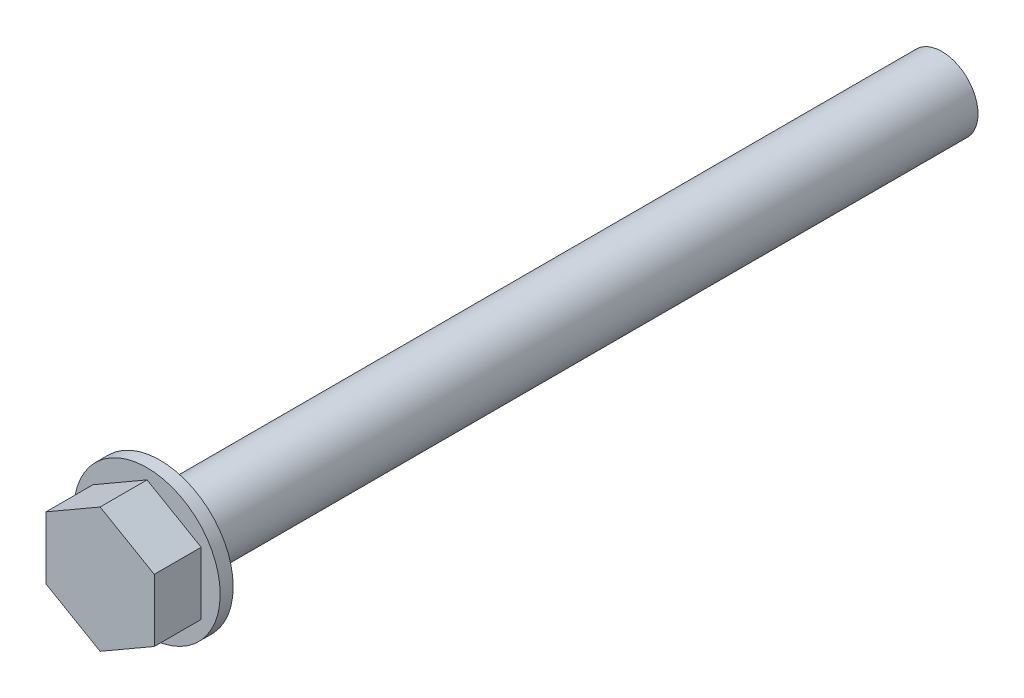
SolidWorks part; units mm, degrees
material "AISI Type 316L stainless steel"
ref_plane "Front Plane" through (0, 0, 0) normal (0, 0, 1) x (1, 0, 0)
ref_plane "Top Plane" through (0, 0, 0) normal (0, 1, 0) x (1, 0, 0)
ref_plane "Right Plane" through (0, 0, 0) normal (1, 0, 0) x (0, 0, -1)
sketch "Extrude sketch 1" plane through (0, 0, 0) normal (0, 0, 1) x (1, 0, 0)
  circle A0 centre (0, 0) radius 12.16
  dimension "D1" = 24.32
extrude "Extrude 1" add sketch "Extrude sketch 1" along normal blind 2.16 separate body
sketch "Extrude sketch 2" plane through (0, 0, 0) normal (0, 0, 1) x (1, 0, 0)
  line L0 (9, 5.1962) -> (0, 10.3923)
  line L1 (0, 10.3923) -> (-9, 5.1962)
  line L2 (-9, 5.1962) -> (-9, -5.1962)
  line L3 (-9, -5.1962) -> (0, -10.3923)
  line L4 (0, -10.3923) -> (9, -5.1962)
  line L5 (9, -5.1962) -> (9, 5.1962)
  dimension "D1" = 9
  dimension "D2" = 5.1962
extrude "Extrude 2" add sketch "Extrude sketch 2" along normal blind 7.8 from offset 2.16 separate body
sketch "Extrude sketch 3" plane through (0, 0, 0) normal (0, 0, 1) x (1, 0, 0)
  circle A0 centre (0, 0) radius 6
  dimension "D1" = 12
extrude "Extrude 3" add sketch "Extrude sketch 3" along normal blind 130.01 from offset 130 separate body offset against normal yes
combine bodies "Combine (weld / assembly of features)" operation type add bodies to combine 103 102 101
